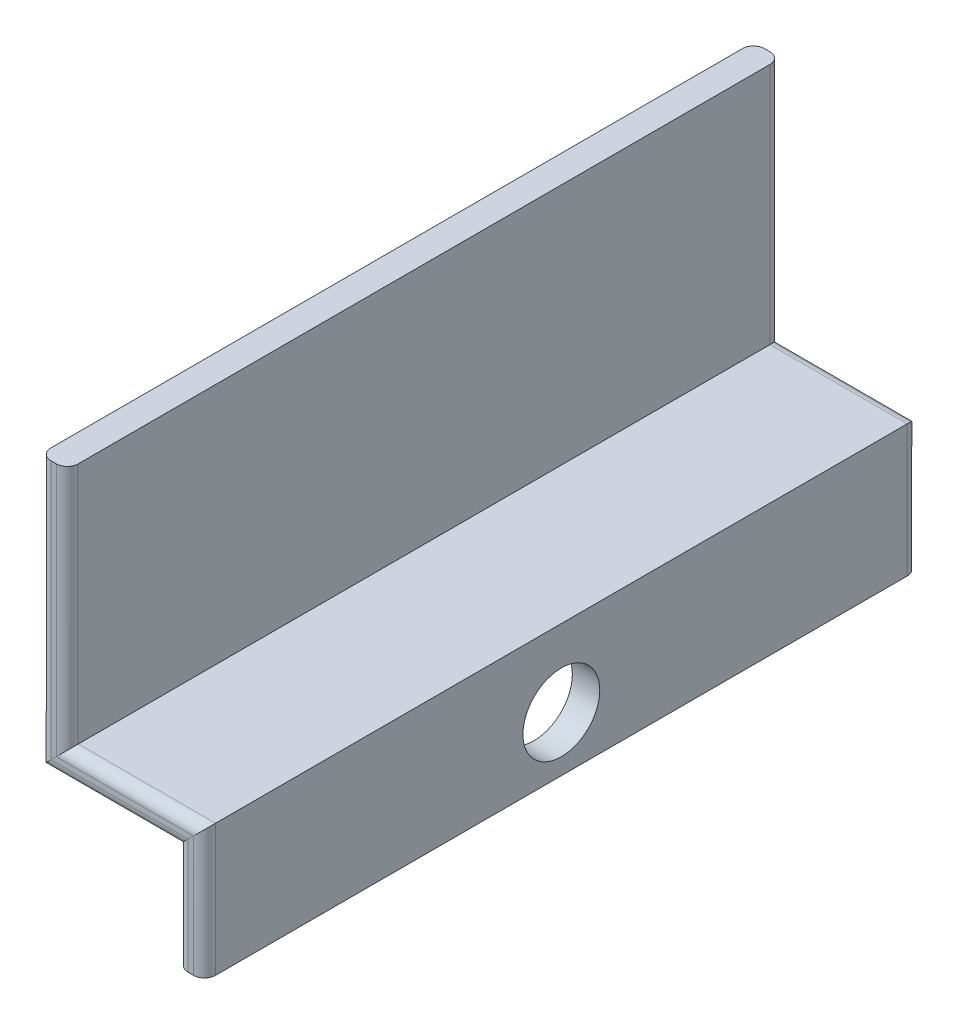
SolidWorks part; units mm, degrees
ref_plane "Front Plane" through (0, 0, 0) normal (0, 0, 1) x (1, 0, 0)
ref_plane "Top Plane" through (0, 0, 0) normal (0, 1, 0) x (1, 0, 0)
ref_plane "Right Plane" through (0, 0, 0) normal (1, 0, 0) x (0, 0, -1)
sketch3d "3DSketch1"
  line L0 (0, 0, 0) -> (0, 21.5, 0)
  line L1 (0, 21.5, 0) -> (-25, 21.5, 0)
  line L2 (-25, 21.5, 0) -> (-25, 68.2, 0)
  line L3 (-25, 68.2, 0) -> (39.395, 68.2, 0) construction
  dimension "D1" = 25
  dimension "D2" = 46.7
  dimension "D3" = 21.5
sketch "Sketch2" plane through (0, 0, 0) normal (0, 1, 0) x (1, 0, 0)
  line L1 (-0.5, 65) -> (0.5, 65)
  line L2 (-2.5, 63) -> (-2.5, -63)
  line L3 (-0.5, -65) -> (0.5, -65)
  line L4 (2.5, 63) -> (2.5, -63)
  line L5 (-2.5, 65) -> (2.5, -65) construction
  line L6 (-2.5, -65) -> (2.5, 65) construction
  arc A0 (0.5, 65) -> (2.5, 63) centre (0.5, 63) cw
  arc A1 (2.5, -63) -> (0.5, -65) centre (0.5, -63) cw
  arc A2 (-0.5, -65) -> (-2.5, -63) centre (-0.5, -63) cw
  arc A3 (-2.5, 63) -> (-0.5, 65) centre (-0.5, 63) cw
  point P0 (0, 0)
  dimension "D3" = 2
  dimension "D1" = 130
  dimension "D2" = 5
sketch "Sketch3" plane through (0, 0, 0) normal (1, 0, 0) x (0, 0, -1)
  line L0 (0, 0) -> (0, 21.5) construction
  circle A0 centre (0, 10) radius 7
  dimension "D1" = 14
  dimension "D2" = 10
sweep "Sweep1" add profiles "Sketch2" path "3DSketch1"
extrude "Cut-Extrude1" cut sketch "Sketch3" against normal through all both and the other way through all
